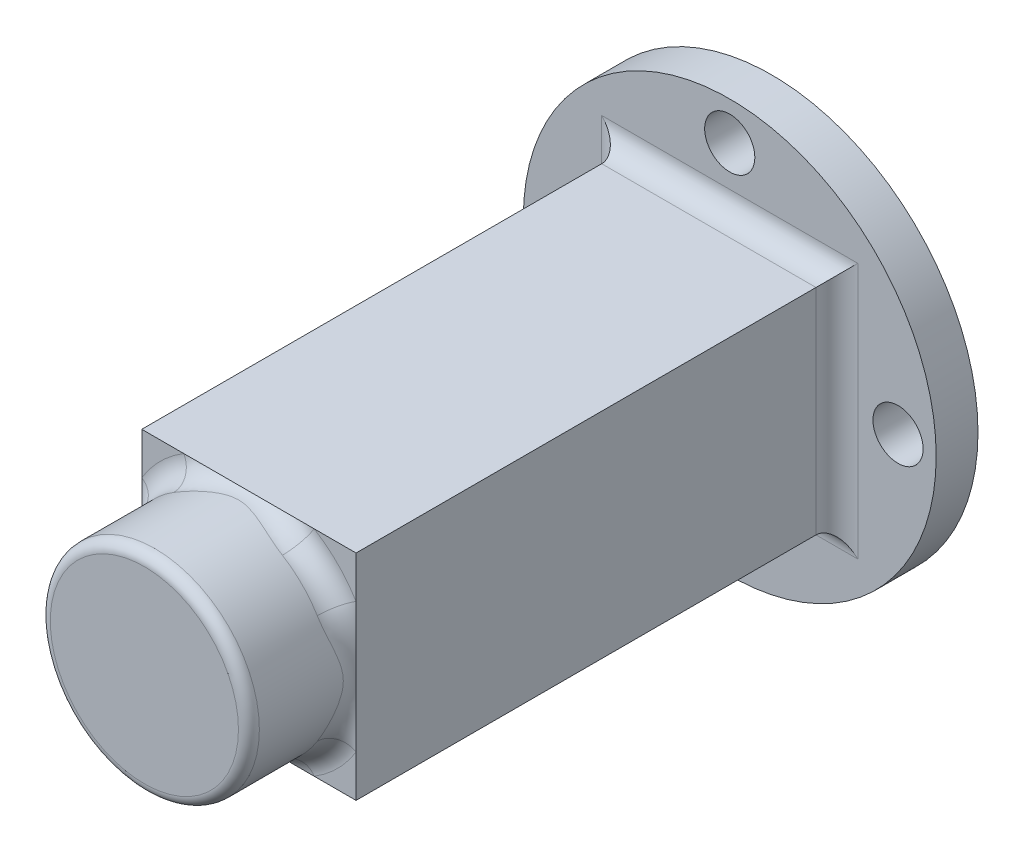
SolidWorks part; units mm, degrees
material "ABS"
ref_plane "Plan de face" through (0, 0, 0) normal (0, 0, 1) x (1, 0, 0)
ref_plane "Plan de dessus" through (0, 0, 0) normal (0, 1, 0) x (1, 0, 0)
ref_plane "Plan de droite" through (0, 0, 0) normal (1, 0, 0) x (0, 0, -1)
sketch "Esquisse1" plane through (0, 0, 0) normal (0, 0, 1) x (1, 0, 0)
  circle A0 centre (0, 0) radius 9.875
  dimension "D1" = 19.75
extrude "Boss.-Extru.1" add sketch "Esquisse1" along normal blind 2
sketch "Esquisse5" plane through (0, 0, 2) normal (0, 0, 1) x (1, 0, 0)
  circle A0 centre (0, 8.0453) radius 1.2
  circle A1 centre (0, -8.0547) radius 1.2
  circle A2 centre (0, 0) radius 9.875 construction
  circle A3 centre (-8.05, 0) radius 1.2
  circle A4 centre (8.05, 0) radius 1.2
  dimension "D1" = 2.4
  dimension "D2" = 2.4
  dimension "D6" = 2.4
  dimension "D7" = 2.4
  dimension "D3" = 16.1
  dimension "D4" = 8.0453
  dimension "D5" = 8.0547
  dimension "D8" = 16.1
  dimension "D9" = 8.05
  dimension "D10" = 8.05
extrude "Enlèv. mat.-Extru.2" cut sketch "Esquisse5" against normal through all
sketch "Esquisse6" plane through (0, 0, 2) normal (0, 0, 1) x (1, 0, 0)
  line L1 (5.125, -5.125) -> (-5.125, -5.125)
  line L2 (5.125, -5.125) -> (5.125, 5.125)
  line L3 (5.125, 5.125) -> (-5.125, 5.125)
  line L4 (-5.125, -5.125) -> (-5.125, 5.125)
  line L5 (5.125, -5.125) -> (-5.125, 5.125) construction
  line L6 (5.125, 5.125) -> (-5.125, -5.125) construction
  point P0 (0, 0)
  dimension "D1" = 10.25
  dimension "D2" = 10.25
extrude "Boss.-Extru.2" add sketch "Esquisse6" along normal blind 23
sketch "Esquisse7" plane through (0, 0, 25) normal (0, 0, 1) x (1, 0, 0)
  circle A0 centre (0, 0) radius 5
  dimension "D1" = 10
extrude "Boss.-Extru.3" add sketch "Esquisse7" along normal blind 5
fillet "Congé1" radius 1 4 edges at (5.125, 0, 2) (0, 5.125, 2) (-5.125, 0, 2) (0, -5.125, 2)
fillet "Congé2" radius 1 1 edges at (5, 0, 25)
fillet "Congé3" radius 0.5 1 edges at (5, 0, 30)
